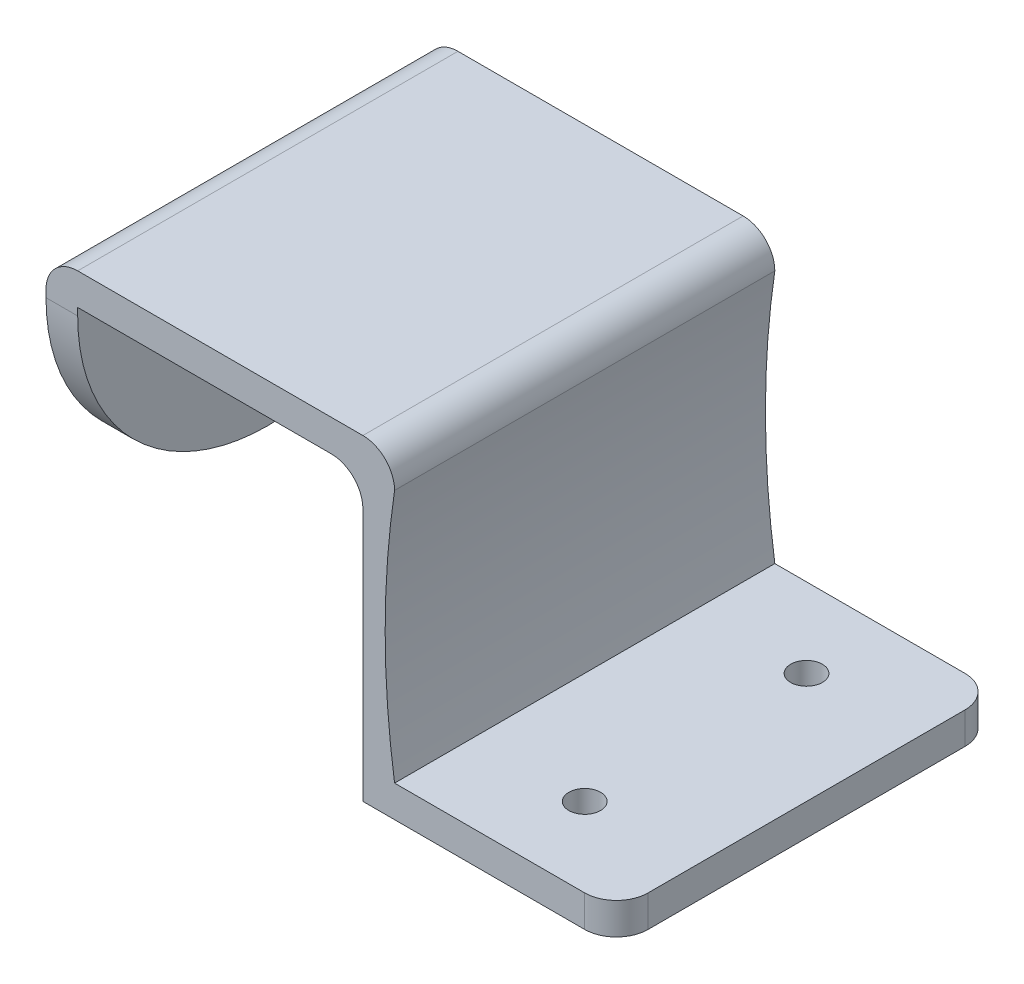
SolidWorks part; units mm, degrees
ref_plane "Front Plane" through (0, 0, 0) normal (0, 0, 1) x (1, 0, 0)
ref_plane "Top Plane" through (0, 0, 0) normal (0, 1, 0) x (1, 0, 0)
ref_plane "Right Plane" through (0, 0, 0) normal (1, 0, 0) x (0, 0, -1)
sketch "Sketch1" plane through (0, 0, 0) normal (0, 0, 1) x (1, 0, 0)
  line L0 (0, 0) -> (-70, 0)
  line L1 (-70, 80) -> (-70, 90)
  line L2 (-70, 90) -> (-170, 90)
  line L3 (0, -10) -> (-80, -10)
  line L4 (-80, -10) -> (-80, 80)
  line L5 (-80, 80) -> (-170, 80)
  line L6 (-170, 90) -> (-170, 80)
  line L7 (0, 0) -> (0, -10)
  line L12 (-70, 0) -> (-70, 90) construction
  line L13 (0, 0) -> (-70, 0) construction
  arc A1 (-70, 80) -> (-70, 0) centre (198.2286, 40) ccw
  dimension "D1" = 100
  dimension "D2" = 90
  dimension "D3" = 70
  dimension "D4" = 10
extrude "Boss-Extrude1" add sketch "Sketch1" along normal blind 120
sketch "Sketch2" plane through (-170, 0, 0) normal (-1, 0, 0) x (0, 0, 1)
  line L0 (0, 80) -> (0, 77.6692)
  line L1 (0, 80) -> (0, -10) construction
  line L3 (120, 80) -> (120, -10) construction
  line L4 (120, 77.6692) -> (120, 90)
  line L5 (120, 90) -> (0, 90)
  line L6 (0, 90) -> (0, 80)
  arc A0 (0, 77.6692) -> (120, 77.6692) centre (60, 77.6692) ccw
extrude "Boss-Extrude2" add sketch "Sketch2" along normal blind 10
sketch "Sketch3" plane through (-180, 0, 0) normal (-1, 0, 0) x (0, 0, 1)
  line L0 (48, 46.9064) -> (72, 46.9064) construction
  line L1 (60, 17.6692) -> (60, 90) construction
  line L2 (120, 90) -> (0, 90) construction
  line L3 (72, 46.9064) -> (60, 67.691) construction
  line L4 (60, 67.691) -> (48, 46.9064) construction
  line L5 (54, 57.2987) -> (72, 46.9064) construction
  line L6 (66, 57.2987) -> (48, 46.9064) construction
  line L7 (60, 46.9064) -> (60, 53.8346) construction
  circle A0 centre (60, 53.8346) radius 9.25
  circle A1 centre (48, 46.9064) radius 1.5
  arc A4 (0, 77.6692) -> (120, 77.6692) centre (60, 77.6692) ccw construction
  circle A5 centre (60, 67.691) radius 1.5
  circle A6 centre (72, 46.9064) radius 1.5
  point P2 (60, 53.8346)
  point P8 (60, 46.9064)
  dimension "D1" = 18.5
  dimension "D3" = 3
  dimension "D2" = 24
extrude "Cut-Extrude1" cut sketch "Sketch3" against normal blind 10
fillet "Fillet1" radius 10 2 edges at (0, -5, 120) (0, -5, 0)
sketch "Sketch4" plane through (0, 0, 0) normal (0, 1, 0) x (1, 0, 0)
  line L0 (-35, -95) -> (-35, -25) construction
  line L1 (0, -110) -> (0, -10) construction
  line L2 (-70, -60) -> (0, -60) construction
  line L3 (-70, -120) -> (-70, 0) construction
  circle A0 centre (-35, -25) radius 5
  circle A1 centre (-35, -95) radius 5
  point P6 (0, -60)
  point P7 (-35, -60)
  point P12 (-35, -60)
  dimension "D2" = 10
  dimension "D1" = 70
extrude "Cut-Extrude2" cut sketch "Sketch4" against normal blind 20
fillet "Fillet2" radius 10 1 edges at (-70, 90, 60)
fillet "Fillet4" radius 10 1 edges at (-80, 80, 60)
fillet "Fillet6" radius 10 1 edges at (-180, 90, 60)
sketch "Sketch5" plane through (-180, 0, 0) normal (-1, 0, 0) x (0, 0, 1)
  circle A0 centre (72, 46.9064) radius 2.5
  circle A1 centre (60, 67.691) radius 2.5
  circle A2 centre (48, 46.9064) radius 2.5
  dimension "D1" = 5
extrude "Cut-Extrude3" cut sketch "Sketch5" against normal blind 5
